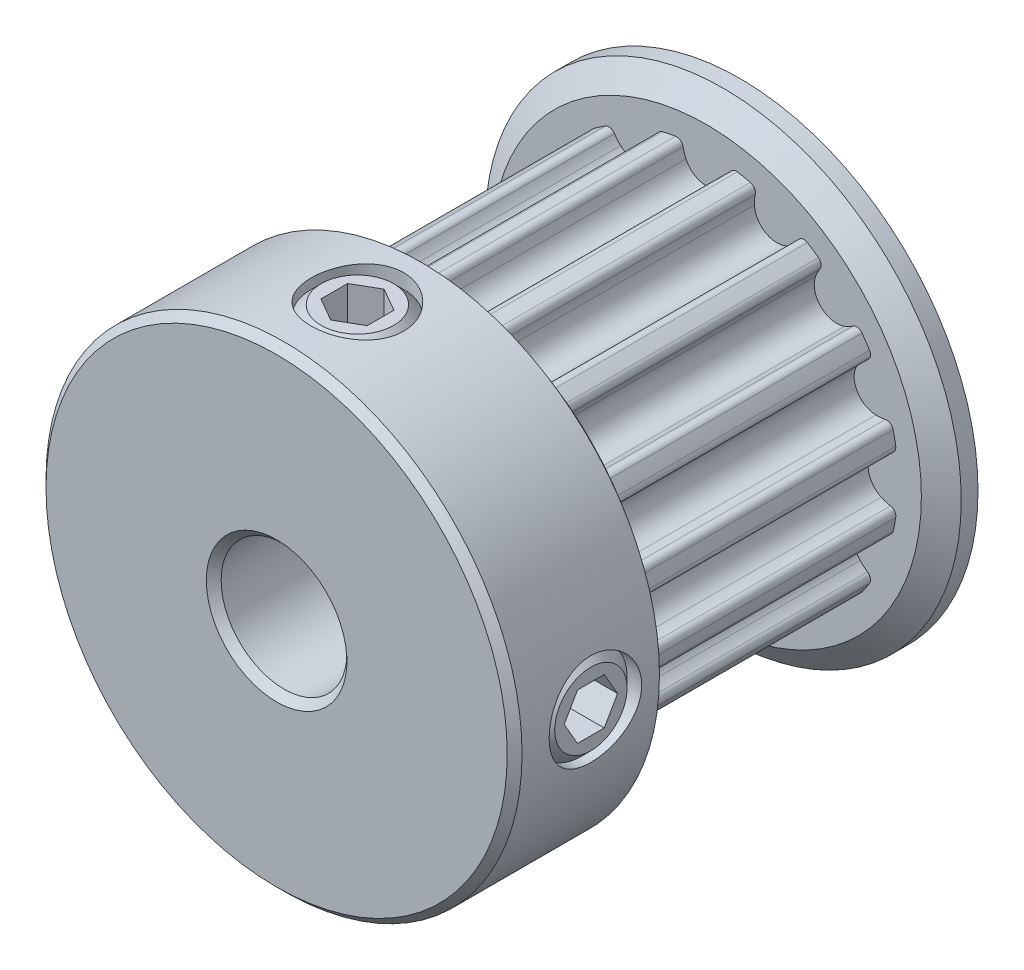
SolidWorks part; units mm, degrees
ref_plane "Front Plane" through (0, 0, 0) normal (0, 0, 1) x (1, 0, 0)
ref_plane "Top Plane" through (0, 0, 0) normal (0, 1, 0) x (1, 0, 0)
ref_plane "Right Plane" through (0, 0, 0) normal (1, 0, 0) x (0, 0, -1)
sketch "Sketch1" plane through (0, 0, 0) normal (0, 0, 1) x (1, 0, 0)
  line L1 (-2.553, 6.1245) -> (2.553, 6.1245) construction
  line L4 (0, 0) -> (0, 6.1245) construction
  line L5 (0, 6.1245) -> (0, 12.0664) construction
  line L6 (0, 7.6455) -> (2.9417, 7.0569) construction
  line L7 (2.9417, 7.0569) -> (3.8741, 6.6682) construction
  line L8 (2.9417, 7.0569) -> (2.553, 6.1245) construction
  line L9 (-2.9417, 7.0569) -> (-2.553, 6.1245) construction
  line L10 (-2.7951, 6.7052) -> (-3.7579, 9.015)
  line L11 (-3.7579, 9.015) -> (3.7579, 9.015)
  line L12 (3.7579, 9.015) -> (2.7951, 6.7052)
  circle A0 centre (0, 0) radius 7.6455 construction
  circle A1 centre (0, 0) radius 9.015 construction
  circle A2 centre (0, 0) radius 7.2645 construction
  arc A3 (-0.7739, 6.6229) -> (0.7739, 6.6229) centre (0, 6.9745) ccw
  arc A4 (-0.7739, 6.6229) -> (-0.8836, 6.9694) centre (0.61, 7.2516) cw
  arc A5 (-2.7951, 6.7052) -> (-1.1695, 7.1697) centre (0, 0) cw
  arc A6 (-0.8836, 6.9694) -> (-1.1695, 7.1697) centre (-1.1292, 6.923) ccw
  arc A7 (2.7951, 6.7052) -> (1.1695, 7.1697) centre (0, 0) ccw
  arc A8 (0.8836, 6.9694) -> (1.1695, 7.1697) centre (1.1292, 6.923) cw
  arc A9 (0.7739, 6.6229) -> (0.8836, 6.9694) centre (-0.61, 7.2516) ccw
  point P6 (0, 20.9083)
  point P11 (0, 7.6455)
  point P13 (0, 9.015)
  point P14 (0, 7.2645)
  dimension "D1" = 8.8419
  dimension "D2" = 4.4209
sketch "Sketch2" plane through (0, 0, 0) normal (1, 0, 0) x (0, 0, -1)
  line L0 (-8.775, 2.3812) -> (8.775, 2.3812)
  line L1 (-8.775, 2.3812) -> (-8.775, 9.015)
  line L2 (-3.29, 9.015) -> (-8.775, 9.015)
  line L3 (-3.925, 2.3813) -> (-3.925, 9.015) construction
  line L4 (-3.925, 9.015) -> (-2.655, 9.015) construction
  line L5 (-2.655, 9.015) -> (-2.655, 7.2645) construction
  line L6 (-2.655, 7.2645) -> (7.505, 7.2645)
  line L7 (7.505, 7.2645) -> (7.505, 9.015) construction
  line L8 (7.505, 9.015) -> (8.775, 9.015) construction
  line L9 (8.775, 9.015) -> (8.775, 2.3812)
  line L10 (-8.775, 0) -> (8.775, 0) construction
  line L11 (8.14, 9.015) -> (7.505, 8.1398)
  line L12 (-2.655, 8.1398) -> (-3.29, 9.015)
  line L14 (-2.655, 8.1398) -> (-2.655, 7.2645)
  line L15 (7.505, 7.2645) -> (7.505, 8.1398)
  line L16 (8.14, 9.015) -> (8.775, 9.015)
  arc A0 (-2.655, 8.1398) -> (-3.29, 9.015) centre (-3.5757, 8.1398) ccw construction
  arc A1 (7.505, 8.1398) -> (8.14, 9.015) centre (8.4257, 8.1398) cw construction
  point P12 (-2.655, 8.1398)
  point P14 (-3.29, 9.015)
  point P20 (7.505, 8.1398)
  point P21 (8.14, 9.015)
  point P25 (7.505, 0)
  point P26 (-2.655, 0)
  dimension "OA" = 17.55
  dimension "Bore" = 4.7625
  dimension "Outside Width" = 11.43
  dimension "Inside Width" = 10.16
revolve "Revolve1" add sketch "Sketch2" angle 360 mid plane about L10
sketch "Sketch3" plane through (0, 0, 0) normal (0, 0, 1) x (1, 0, 0)
  line L6 (3.7579, 9.015) -> (-3.7579, 9.015)
  line L7 (2.7951, 6.7052) -> (3.7579, 9.015)
  line L8 (-3.7579, 9.015) -> (-2.7951, 6.7052)
  line L9 (3.7579, 9.015) -> (-3.7579, 9.015)
  line L10 (2.7951, 6.7052) -> (3.7579, 9.015)
  line L11 (-3.7579, 9.015) -> (-2.7951, 6.7052)
  arc A8 (2.7951, 6.7052) -> (1.1695, 7.1697) centre (0, 0) ccw
  arc A9 (1.1695, 7.1697) -> (0.8836, 6.9694) centre (1.1292, 6.923) ccw
  arc A10 (0.7739, 6.6229) -> (0.8836, 6.9694) centre (-0.61, 7.2516) ccw
  arc A11 (-0.7739, 6.6229) -> (0.7739, 6.6229) centre (0, 6.9745) ccw
  arc A12 (-0.8836, 6.9694) -> (-0.7739, 6.6229) centre (0.61, 7.2516) ccw
  arc A13 (-0.8836, 6.9694) -> (-1.1695, 7.1697) centre (-1.1292, 6.923) ccw
  arc A14 (-1.1695, 7.1697) -> (-2.7951, 6.7052) centre (0, 0) ccw
  arc A15 (2.7951, 6.7052) -> (1.1695, 7.1697) centre (0, 0) ccw
  arc A16 (1.1695, 7.1697) -> (0.8836, 6.9694) centre (1.1292, 6.923) ccw
  arc A17 (0.7739, 6.6229) -> (0.8836, 6.9694) centre (-0.61, 7.2516) ccw
  arc A18 (-0.7739, 6.6229) -> (0.7739, 6.6229) centre (0, 6.9745) ccw
  arc A19 (-0.8836, 6.9694) -> (-0.7739, 6.6229) centre (0.61, 7.2516) ccw
  arc A20 (-0.8836, 6.9694) -> (-1.1695, 7.1697) centre (-1.1292, 6.923) ccw
  arc A21 (-1.1695, 7.1697) -> (-2.7951, 6.7052) centre (0, 0) ccw
  dimension "D1" = 0
extrude "Cut-Extrude1" cut sketch "Sketch3" against normal up to vertex (7.505 mm away) from vertex up to point (0, 7.2645, -7.505) starting at point (0, 7.2645, 2.655)
pattern_circular "CirPattern1" count 16 over 360 about axis through (0, 0, 8.775) along (0, 0, 1) of "Cut-Extrude1"
sketch "Sketch4" plane through (0, 0, 0) normal (1, 0, 0) x (0, -1, 0)
  line L0 (0, -2.655) -> (0, -8.775) construction
  line L1 (-2.3812, -8.775) -> (2.3812, -8.775) construction
  line L2 (8.1398, -2.655) -> (-8.1398, -2.655) construction
  circle A0 centre (0, -5.715) radius 1.7526
extrude "Cut-Extrude2" cut sketch "Sketch4" along normal through all
ref_plane "Plane1" through (0, 0, 5.715) normal (0, 0, 1) x (1, 0, 0)
sketch "Sketch5" plane through (0, 0, 5.715) normal (0, 0, 1) x (1, 0, 0)
  line L0 (0, 0) -> (0, 9.015) construction
  line L1 (2.3812, -1.3716) -> (2.3812, 0)
  line L2 (2.7622, -1.7526) -> (8.462, -1.7526)
  line L3 (2.3812, 0) -> (9.015, 0) construction
  line L4 (2.3812, 0) -> (8.843, 0)
  line L5 (8.843, 0) -> (8.843, -1.3716)
  line L6 (2.7622, -1.7526) -> (2.3812, -1.3716)
  line L7 (8.843, -1.3716) -> (8.462, -1.7526)
  circle A0 centre (0, 0) radius 9.015 construction
  circle A1 centre (0, 0) radius 2.3812 construction
  point P2 (2.3812, -1.7526)
  point P11 (8.843, -1.7526)
revolve "Revolve2" add sketch "Sketch5" angle 360 mid plane about L4
sketch "Sketch6" plane through (8.843, 5.3841, 0) normal (-1, 0, 0) x (0, -1, 0)
  line L1 (5.3841, 6.7269) -> (4.5078, 6.2209)
  line L2 (4.5078, 6.2209) -> (4.5078, 5.2091)
  line L3 (4.5078, 5.2091) -> (5.3841, 4.7031)
  line L4 (5.3841, 4.7031) -> (6.2604, 5.2091)
  line L5 (6.2604, 5.2091) -> (6.2604, 6.2209)
  line L6 (6.2604, 6.2209) -> (5.3841, 6.7269)
  circle A0 centre (5.3841, 5.715) radius 0.8763 construction
  dimension "D1" = 1.7526
extrude "Cut-Extrude3" cut sketch "Sketch6" along normal blind 1.3144
pattern_circular "CirPattern3" count 2 over 90 about axis through (0, 0, 8.775) along (0, 0, 1) of "Cut-Extrude2", "Revolve2", "Cut-Extrude3"
chamfer "Chamfer1" distance 0.2807 angle 45 2 edges at (2.3812, 0, 8.775) (9.015, 0, 8.775)
ref_axis "Center Axis 1" through (0, 0, -8.775) along (0, 0, 1)
ref_plane "Contact Plane 1" through (0, 0, 8.775) normal (0, 0, 1) x (1, 0, 0)
ref_plane "Contact Plane 2" through (0, 0, -8.775) normal (0, 0, -1) x (-1, 0, 0)
equation "\"D2@Sketch1\"= \"D1@Sketch1\" / 2"
equation "\"D1@Sketch6\" = \"Set Screw@Sketch4\" / 2"
equation "\"D1@Cut-Extrude3\" = \"D1@Sketch6\"*.75"
